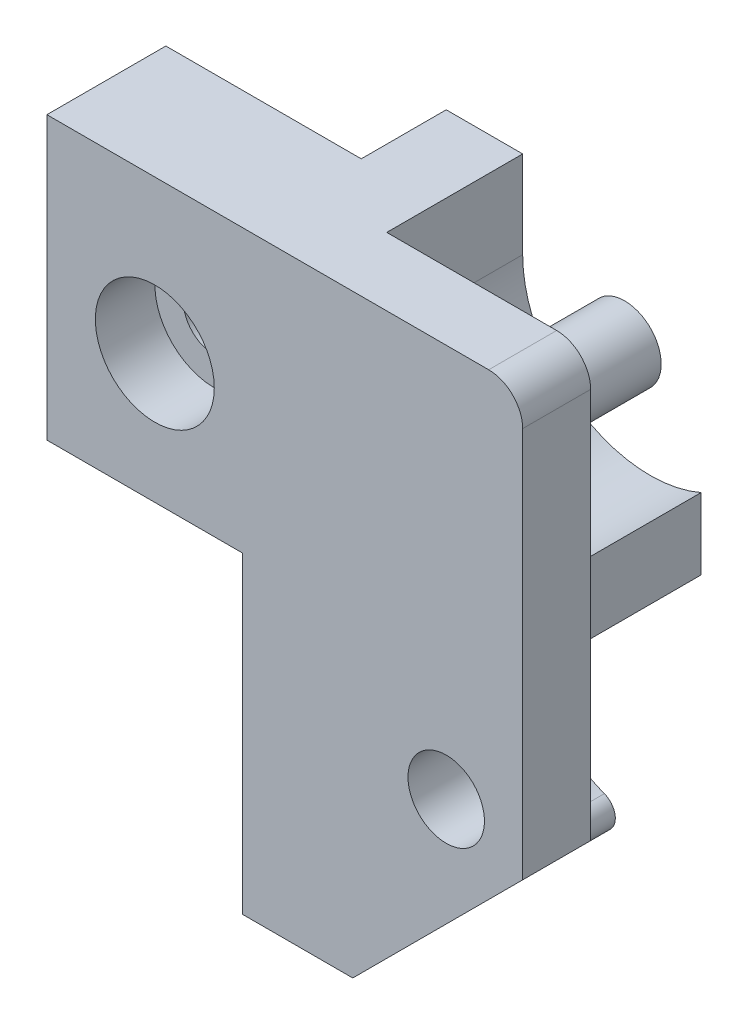
SolidWorks part; units mm, degrees
note: The reader was unsure of these and kept them because the rebuilt part matched: shared geometry of "Sketch2<3>", "Sketch2<5>".
material "ABS"
ref_plane "Front Plane" through (0, 0, 0) normal (0, 0, 1) x (1, 0, 0)
ref_plane "Top Plane" through (0, 0, 0) normal (0, 1, 0) x (1, 0, 0)
ref_plane "Right Plane" through (0, 0, 0) normal (1, 0, 0) x (0, 0, -1)
sketch "Sketch1" plane through (0, 0, 0) normal (0, 0, 1) x (1, 0, 0)
  line L0 (18, 0) -> (28, 10)
  line L1 (0, 0) -> (18, 0)
  line L2 (0, 0) -> (0, 35)
  line L3 (0, 35) -> (26, 35)
  line L4 (28, 10) -> (28, 33)
  arc A0 (28, 33) -> (26, 35) centre (26, 33) ccw
  point P3 (28, 0)
  dimension "D1" = 2
  dimension "D2" = 35
  dimension "D3" = 28
extrude "Boss-Extrude1" add sketch "Sketch1" along normal blind 4
sketch "Sketch2" plane through (0, 0, 0) normal (0, 0, -1) x (-1, 0, 0)
  line L0 (-23.5, 11.864) -> (-23.5, 29.864) construction
  line L1 (-28, 10) -> (-28, 33) construction
  line L2 (-18, 0) -> (-28, 10) construction
  line L3 (-21.1583, 3.1583) -> (-18, 0)
  line L4 (-26.5, 22.9901) -> (-26.5, 18.7923)
  line L5 (-15.95, 18.414) -> (-23.5, 18.414)
  line L6 (-15.95, 18.414) -> (-15.95, 5.314)
  line L7 (-15.95, 5.314) -> (-23.5, 5.314)
  line L8 (-23.5, 18.414) -> (-23.5, 5.314)
  line L9 (-16, 29.864) -> (-16, 35)
  line L10 (-26, 35) -> (0, 35) construction
  line L11 (-16, 35) -> (-18.0346, 35)
  circle A0 centre (-23.5, 29.864) radius 2.15
  circle A1 centre (-23.5, 11.864) radius 2.25
  circle A2 centre (-23.5, 11.864) radius 7.55
  circle A3 centre (-23.5, 29.864) radius 7.5
  arc A4 (-19.725, 5.314) -> (-20.8073, 4.7998) centre (-23.5, 11.864) cw
  arc A5 (-21.1583, 3.1583) -> (-20.8073, 4.7998) centre (-20.4511, 3.8654) cw
  dimension "D1" = 4.3
  dimension "D2" = 4.5
  dimension "D5" = 15.1
  dimension "D3" = 15
  dimension "D8" = 1
  dimension "D4" = 18
  dimension "D6" = 13.1
  dimension "D7" = 1.5
extrude "Cut-Extrude1" cut sketch "Sketch2" against normal through all contours A1
extrude "Boss-Extrude2" add sketch "Sketch2<3>" along normal blind 8 contours A0
sketch "Sketch2<3>" plane through (0, 0, 0) normal (0, 0, -1) x (-1, 0, 0) same geometry as "Sketch2"
extrude "Boss-Extrude4" add sketch "Sketch2<5>" along normal up to surface (8 mm away)
sketch "Sketch2<5>" plane through (0, 0, 0) normal (0, 0, -1) x (-1, 0, 0) same geometry as "Sketch2"
sketch "Sketch6" plane through (0, 0, -8) normal (0, 0, -1) x (-1, 0, 0)
  line L0 (-15.95, 18.414) -> (-19.745, 18.414) construction
  line L1 (0, 0) -> (-11.5, 0)
  line L2 (0, 0) -> (0, 18.414)
  line L3 (0, 18.414) -> (-11.5, 18.414)
  line L4 (-11.5, 0) -> (-11.5, 18.414)
  dimension "D1" = 11.5
extrude "Cut-Extrude2" cut sketch "Sketch6" against normal through all
sketch "Sketch12" plane through (15.95, 0, 0) normal (1, 0, 0) x (0, 0, -1)
  line L4 (0, 18.414) -> (0, 5.314)
  line L5 (0, 5.314) -> (8, 5.314)
  line L6 (8, 5.314) -> (8, 18.414)
  line L7 (8, 18.414) -> (0, 18.414)
  line L8 (0, 18.414) -> (0, 5.314)
  line L9 (0, 5.314) -> (8, 5.314)
  line L10 (8, 5.314) -> (8, 18.414)
  line L11 (8, 18.414) -> (0, 18.414)
  dimension "D1" = 0
extrude "Cut-Extrude3" cut sketch "Sketch12" against normal through all
sketch "Sketch3" plane through (0, 0, 4) normal (0, 0, 1) x (1, 0, 0)
  line L5 (0, 18.414) -> (19.745, 18.414)
  line L6 (0, 35) -> (0, 18.414)
  line L7 (16, 35) -> (0, 35)
  line L8 (16, 29.864) -> (16, 35)
  line L9 (26.5, 18.7923) -> (26.5, 22.9901)
  line L10 (0, 18.414) -> (19.745, 18.414)
  line L11 (0, 35) -> (0, 18.414)
  line L12 (16, 35) -> (0, 35)
  line L13 (16, 29.864) -> (16, 35)
  line L14 (26.5, 18.7923) -> (26.5, 22.9901)
  circle A0 centre (6.35, 26) radius 3.5
  arc A3 (16, 29.864) -> (26.5, 22.9901) centre (23.5, 29.864) ccw
  arc A4 (26.5, 18.7923) -> (19.745, 18.414) centre (23.5, 11.864) ccw
  arc A5 (16, 29.864) -> (26.5, 22.9901) centre (23.5, 29.864) ccw
  arc A6 (26.5, 18.7923) -> (19.745, 18.414) centre (23.5, 11.864) ccw
  dimension "D2" = 7
  dimension "D3" = 6.35
  dimension "D4" = 9
  dimension "D1" = 0
hole_wizard "CBORE for #6 Socket Head Cap Screw1" positions "Sketch5" profile "Sketch4" counterbore size "#6" standard "ANSI Inch" end condition through all
sketch "Sketch5" plane through (0, 0, 4) normal (0, 0, 1) x (1, 0, 0)
  point P0 (6.35, 26)
sketch "Sketch4" plane through (6.35, 26, 4) normal (1, 0, 0) x (0, -1, 0)
  line L0 (0, 0) -> (0, 12)
  line L1 (0, 12) -> (1.8288, 12)
  line L3 (1.8288, 12) -> (1.8288, 3.5052)
  line L4 (1.8288, 3.5052) -> (3.5, 3.5052)
  line L5 (3.5, 3.5052) -> (3.5, 0)
  line L7 (3.5, 0) -> (0, 0)
  line L11 (0, -6.35) -> (0, 107.95) construction
  dimension "Thru Hole Dia." = 3.6576
  dimension "Thru Hole Depth" = 12
  dimension "C'Bore Dia." = 7
  dimension "C'Bore Depth" = 3.5052
sketch "Sketch13" plane through (0, 0, -8) normal (0, 0, -1) x (-1, 0, 0)
  line L1 (0, 18.414) -> (-11.5, 18.414)
  line L2 (0, 18.414) -> (0, 35)
  line L3 (0, 35) -> (-11.5, 35)
  line L4 (-11.5, 18.414) -> (-11.5, 35)
  line L5 (0, 35) -> (-16, 35) construction
  line L7 (-11.5, 5.314) -> (-11.5, 0)
extrude "Cut-Extrude4" cut sketch "Sketch13" against normal blind 5
sketch "Sketch14" plane through (0, 0, -8) normal (0, 0, -1) x (-1, 0, 0)
  circle A0 centre (-23.5, 29.864) radius 2.15
extrude "Cut-Extrude5" cut sketch "Sketch14" against normal blind 1.5
